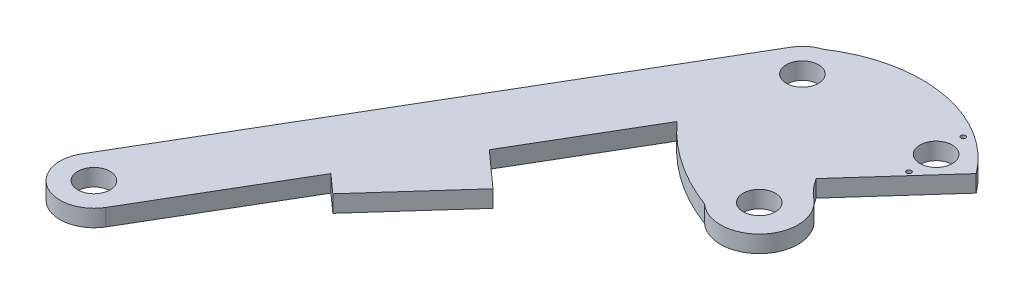
SolidWorks part; units mm, degrees
material "Cedro"
ref_plane "Alzado" through (0, 0, 0) normal (0, 0, 1) x (1, 0, 0)
ref_plane "Planta" through (0, 0, 0) normal (0, 1, 0) x (1, 0, 0)
ref_plane "Vista lateral" through (0, 0, 0) normal (1, 0, 0) x (0, 0, -1)
sketch "Croquis1" plane through (0, 0, 0) normal (0, 1, 0) x (1, 0, 0)
  line L0 (2.7441, 395.2665) -> (-229.13, 0) construction
  line L3 (28.6203, 380.0868) -> (-203.2538, -15.1797)
  line L4 (-23.1321, 410.4462) -> (-255.0062, 15.1797)
  arc A3 (28.6203, 380.0868) -> (-23.1321, 410.4462) centre (2.7441, 395.2665) ccw
  arc A4 (-255.0062, 15.1797) -> (-203.2538, -15.1797) centre (-229.13, 0) ccw
  point P2 (0, 0)
  point P4 (-113.193, 197.6333)
  dimension "D2" = 30
  dimension "D1" = 231.8741
extrude "Saliente-Extruir1" add sketch "Croquis1" along normal blind 15
sketch "Croquis3" plane through (0, 15, 0) normal (0, 1, 0) x (1, 0, 0)
  circle A0 centre (-229.13, 0) radius 14.29
  circle A1 centre (2.7441, 395.2665) radius 14.29
  dimension "D1" = 28.58
  dimension "D2" = 28.58
extrude "Cortar-Extruir2" cut sketch "Croquis3" against normal through all
sketch "Croquis4" plane through (0, 15, 0) normal (0, 1, 0) x (1, 0, 0)
  line L0 (-113.2889, 95.6285) -> (-129.646, 110.2966)
  line L1 (-203.2538, -15.1797) -> (28.6203, 380.0868) construction
  line L2 (-129.646, 110.2966) -> (-77.8157, 198.6497)
  line L3 (-46.2717, 170.3629) -> (-35.1042, 160.3486) construction
  line L4 (-77.8157, 198.6497) -> (-46.2717, 170.3629)
  line L5 (-46.2717, 170.3629) -> (-113.2889, 95.6285)
extrude "Saliente-Extruir2" add sketch "Croquis4" against normal through all
sketch "Croquis5" plane through (0, 15, 0) normal (0, 1, 0) x (1, 0, 0)
  line L0 (155.9528, 395.874) -> (88.9356, 321.1396)
  line L1 (-23.1321, 410.4462) -> (17.0937, 410.4462)
  line L2 (17.0937, 410.4462) -> (21.6145, 387.9873)
  line L3 (21.6145, 387.9873) -> (11.4593, 350.8332)
  arc A0 (88.9356, 321.1396) -> (11.4593, 350.8332) centre (21.6145, 261.408) ccw
  arc A1 (-6.4312, 423.829) -> (155.9528, 395.874) centre (59.9583, 323.8668) cw
  arc A2 (-6.4312, 423.829) -> (-23.1321, 410.4462) centre (2.7441, 395.2665) ccw
extrude "Saliente-Extruir3" add sketch "Croquis5" against normal through all
sketch "Croquis6" plane through (0, 15, 0) normal (0, 1, 0) x (1, 0, 0)
  circle A0 centre (123.4484, 392.9164) radius 14.29
  dimension "D1" = 28.58
extrude "Cortar-Extruir3" cut sketch "Croquis6" against normal through all
sketch "Croquis7" plane through (0, 15, 0) normal (0, 1, 0) x (1, 0, 0)
  circle A0 centre (122.0676, 418.2789) radius 2.07
  circle A1 centre (124.8292, 367.554) radius 2.07
  dimension "D1" = 4.14
  dimension "D2" = 4.14
extrude "Cortar-Extruir4" cut sketch "Croquis7" against normal through all
sketch "Croquis10" plane through (0, 15, 0) normal (0, 1, 0) x (1, 0, 0)
  line L0 (82.1163, 277.7004) -> (44.3114, 311.6014) construction
  line L1 (44.3114, 311.6014) -> (82.1163, 277.7004) construction
  line L2 (82.1163, 277.7004) -> (118.5924, 318.3768) construction
  line L3 (118.5924, 318.3768) -> (53.2233, 245.4803) construction
  line L4 (-77.8157, 198.6497) -> (11.4593, 350.8332) construction
  line L5 (-16.3701, 303.3935) -> (0, 363.5793)
  line L6 (0, 363.5793) -> (88.9356, 352.9429)
  line L7 (88.9356, 352.9429) -> (88.9356, 321.1396)
  circle A0 centre (82.1163, 277.7004) radius 14.29
  arc A1 (58.975, 252.3965) -> (105.009, 303.2293) centre (82.1163, 277.7004) ccw
  arc A2 (105.009, 303.2293) -> (88.9356, 321.1396) centre (148.2938, 358.2423) cw
  arc A3 (58.975, 252.3965) -> (-16.3701, 303.3935) centre (124.7042, 430.6651) cw
  dimension "D1" = 28.58
  dimension "D2" = 20
  dimension "D3" = 70
  dimension "D5" = 190
  dimension "D4" = 55
extrude "Saliente-Extruir4" add sketch "Croquis10" against normal through all
